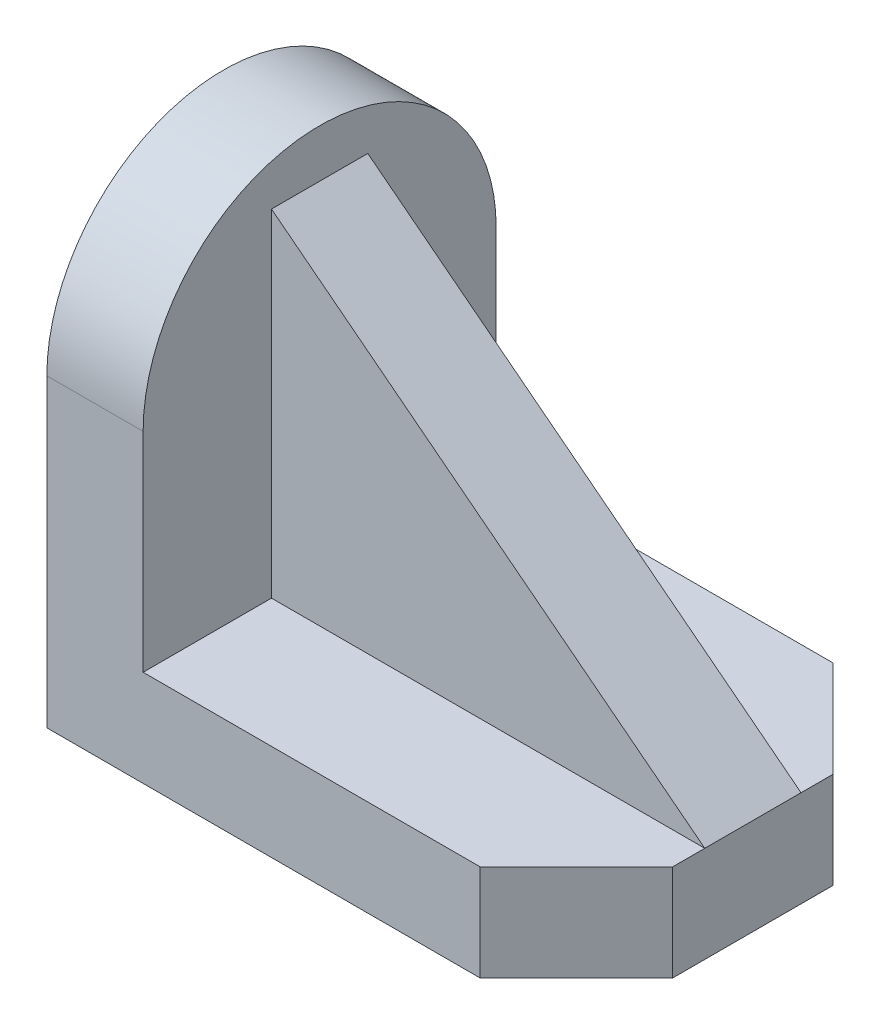
SolidWorks part; units mm, degrees
ref_plane "Front Plane" through (0, 0, 0) normal (0, 0, 1) x (1, 0, 0)
ref_plane "Top Plane" through (0, 0, 0) normal (0, 1, 0) x (1, 0, 0)
ref_plane "Right Plane" through (0, 0, 0) normal (1, 0, 0) x (0, 0, -1)
sketch "Sketch1" plane through (0, 0, 0) normal (0, 1, 0) x (1, 0, 0)
  line L1 (-33, -22) -> (33, -22)
  line L2 (-33, -22) -> (-33, 22)
  line L3 (-33, 22) -> (33, 22)
  line L4 (33, -22) -> (33, 22)
  line L5 (-33, -22) -> (33, 22) construction
  line L6 (-33, 22) -> (33, -22) construction
  point P0 (0, 0)
  dimension "D1" = 66
  dimension "D2" = 44
extrude "Boss-Extrude1" add sketch "Sketch1" along normal blind 12
chamfer "Chamfer1" distance 12 angle 45 2 edges at (33, 6, -22) (33, 6, 22)
sketch "Sketch2" plane through (-33, 0, 0) normal (-1, 0, 0) x (0, 0, 1)
  line L1 (-22, 12) -> (22, 12)
  line L2 (-22, 12) -> (-22, 60)
  line L3 (-22, 60) -> (22, 60)
  line L4 (22, 12) -> (22, 60)
  line L5 (22, 12) -> (22, 0) construction
  dimension "D1" = 48
extrude "Boss-Extrude2" add sketch "Sketch2" against normal blind 12
fillet "Fillet1" 2 edges at (-27, 60, 22) (-27, 60, -22) type full round first side face at (-11, 24, 22) second side face at (-11, 24, -22) middle face at (-27, 60, 0)
sketch "Sketch4" plane through (0, 0, 0) normal (0, 0, 1) x (1, 0, 0)
  line L0 (-21, 54) -> (33, 12)
  line L1 (-21, 38) -> (-21, 60) construction
  line L2 (33, 12) -> (-21, 12)
  line L3 (-21, 12) -> (-21, 54)
  dimension "D1" = 42
extrude "Boss-Extrude3" add sketch "Sketch4" along normal mid plane 12
